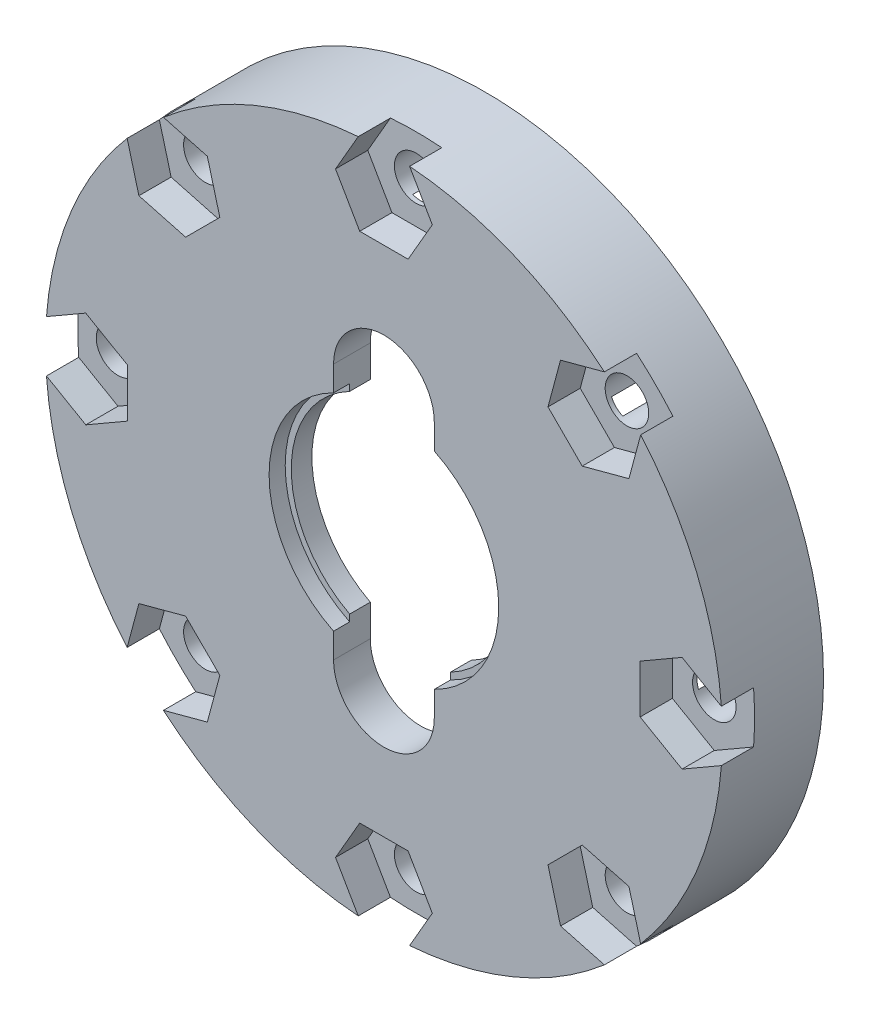
SolidWorks part; units mm, degrees
ref_plane "Front Plane" through (0, 0, 0) normal (0, 0, 1) x (1, 0, 0)
ref_plane "Top Plane" through (0, 0, 0) normal (0, 1, 0) x (1, 0, 0)
ref_plane "Right Plane" through (0, 0, 0) normal (1, 0, 0) x (0, 0, -1)
ref_axis "Z" through (0, 0, -6.594) along (0, 0, 1)
sketch "Sketch3" plane through (0, 0, 0) normal (0, 0, 1) x (1, 0, 0)
  line L0 (-3.125, -6.4031) -> (-3.125, -7.9497)
  line L1 (-3.125, -7.9497) -> (3.125, -7.9497)
  line L2 (3.125, -7.9497) -> (3.125, -6.4031)
  line L3 (3.125, 6.4031) -> (3.125, 7.9494)
  line L4 (3.125, 7.9494) -> (-3.125, 7.9494)
  line L5 (-3.125, 7.9494) -> (-3.125, 6.4031)
  line L132 (3.05, 6.3548) -> (3.05, 6.3561) construction
  line L133 (-3.05, 6.3561) -> (-3.05, 6.3548) construction
  line L134 (3.05, -6.3561) -> (3.05, -6.355) construction
  line L135 (-3.05, -6.355) -> (-3.05, -6.3561) construction
  line L198 (3.05, 6.3548) -> (3.05, 7.8744)
  line L199 (3.05, 7.8744) -> (-3.05, 7.8744)
  line L200 (-3.05, 7.8744) -> (-3.05, 6.3548)
  line L201 (-3.05, 6.3548) -> (-3.4914, 6.1247)
  line L202 (-3.4914, 6.1247) -> (-3.9416, 5.8451)
  line L203 (-3.9416, 5.8451) -> (-4.3696, 5.5325)
  line L204 (-4.3696, 5.5325) -> (-4.7729, 5.1886)
  line L205 (-4.7729, 5.1886) -> (-5.1492, 4.8154)
  line L206 (-5.1492, 4.8154) -> (-5.4964, 4.4149)
  line L207 (-5.4964, 4.4149) -> (-5.8125, 3.9896)
  line L208 (-5.8125, 3.9896) -> (-6.0958, 3.5417)
  line L209 (-6.0958, 3.5417) -> (-6.3446, 3.0737)
  line L210 (-6.3446, 3.0737) -> (-6.5576, 2.5884)
  line L211 (-6.5576, 2.5884) -> (-6.7335, 2.0885)
  line L212 (-6.7335, 2.0885) -> (-6.8714, 1.5768)
  line L213 (-6.8714, 1.5768) -> (-6.9705, 1.0561)
  line L214 (-6.9705, 1.0561) -> (-7.0301, 0.5295)
  line L215 (-7.0301, 0.5295) -> (-7.05, -0.0001)
  line L216 (-7.05, -0.0001) -> (-7.0301, -0.5297)
  line L217 (-7.0301, -0.5297) -> (-6.9705, -1.0563)
  line L218 (-6.9705, -1.0563) -> (-6.8714, -1.577)
  line L219 (-6.8714, -1.577) -> (-6.7335, -2.0887)
  line L220 (-6.7335, -2.0887) -> (-6.5576, -2.5887)
  line L221 (-6.5576, -2.5887) -> (-6.3446, -3.074)
  line L222 (-6.3446, -3.074) -> (-6.0958, -3.5419)
  line L223 (-6.0958, -3.5419) -> (-5.8125, -3.9898)
  line L224 (-5.8125, -3.9898) -> (-5.4964, -4.4152)
  line L225 (-5.4964, -4.4152) -> (-5.1492, -4.8156)
  line L226 (-5.1492, -4.8156) -> (-4.7729, -5.1888)
  line L227 (-4.7729, -5.1888) -> (-4.3696, -5.5327)
  line L228 (-4.3696, -5.5327) -> (-3.9416, -5.8453)
  line L229 (-3.9416, -5.8453) -> (-3.4914, -6.1249)
  line L230 (-3.4914, -6.1249) -> (-3.05, -6.355)
  line L231 (-3.05, -6.355) -> (-3.05, -7.8747)
  line L232 (-3.05, -7.8747) -> (3.05, -7.8747)
  line L233 (3.05, -7.8747) -> (3.05, -6.355)
  line L234 (3.05, -6.355) -> (3.4914, -6.1249)
  line L235 (3.4914, -6.1249) -> (3.9417, -5.8453)
  line L236 (3.9417, -5.8453) -> (4.3696, -5.5327)
  line L237 (4.3696, -5.5327) -> (4.7729, -5.1888)
  line L238 (4.7729, -5.1888) -> (5.1492, -4.8156)
  line L239 (5.1492, -4.8156) -> (5.4964, -4.4152)
  line L240 (5.4964, -4.4152) -> (5.8125, -3.9898)
  line L241 (5.8125, -3.9898) -> (6.0958, -3.5419)
  line L242 (6.0958, -3.5419) -> (6.3447, -3.074)
  line L243 (6.3447, -3.074) -> (6.5576, -2.5887)
  line L244 (6.5576, -2.5887) -> (6.7336, -2.0887)
  line L245 (6.7336, -2.0887) -> (6.8714, -1.577)
  line L246 (6.8714, -1.577) -> (6.9705, -1.0563)
  line L247 (6.9705, -1.0563) -> (7.0301, -0.5297)
  line L248 (7.0301, -0.5297) -> (7.05, -0.0001)
  line L249 (7.05, -0.0001) -> (7.0301, 0.5295)
  line L250 (7.0301, 0.5295) -> (6.9705, 1.0561)
  line L251 (6.9705, 1.0561) -> (6.8714, 1.5768)
  line L252 (6.8714, 1.5768) -> (6.7336, 2.0885)
  line L253 (6.7336, 2.0885) -> (6.5576, 2.5884)
  line L254 (6.5576, 2.5884) -> (6.3447, 3.0737)
  line L255 (6.3447, 3.0737) -> (6.0958, 3.5417)
  line L256 (6.0958, 3.5417) -> (5.8125, 3.9896)
  line L257 (5.8125, 3.9896) -> (5.4964, 4.4149)
  line L258 (5.4964, 4.4149) -> (5.1492, 4.8154)
  line L259 (5.1492, 4.8154) -> (4.7729, 5.1886)
  line L260 (4.7729, 5.1886) -> (4.3696, 5.5325)
  line L261 (4.3696, 5.5325) -> (3.9417, 5.8451)
  line L262 (3.9417, 5.8451) -> (3.4914, 6.1247)
  line L263 (3.4914, 6.1247) -> (3.05, 6.3548)
  line L264 (3.05, 6.3561) -> (3.05, 7.8744) construction
  line L265 (3.05, 7.8744) -> (-3.05, 7.8744) construction
  line L266 (-3.05, 7.8744) -> (-3.05, 6.3561) construction
  line L297 (-3.05, -6.3561) -> (-3.05, -7.8747) construction
  line L298 (-3.05, -7.8747) -> (3.05, -7.8747) construction
  line L299 (3.05, -7.8747) -> (3.05, -6.3561) construction
  arc A1 (-3.05, 6.3561) -> (-3.05, -6.3561) centre (0, 0) ccw construction
  arc A2 (3.05, 6.3561) -> (-3.05, 6.3561) centre (0, 0) ccw construction
  arc A3 (3.05, -6.3561) -> (3.05, 6.3561) centre (0, 0) ccw construction
  arc A4 (-3.05, -6.3561) -> (3.05, -6.3561) centre (0, 0) ccw construction
  circle A5 centre (0, 0) radius 21
  arc A6 (-3.125, 6.4031) -> (-3.125, -6.4031) centre (0, 0) ccw
  arc A7 (3.125, -6.4031) -> (3.125, 6.4031) centre (0, 0) ccw
  dimension "D1" = 14.1
  dimension "D3" = 42
  dimension "D2" = 0.075
  dimension "D4" = 0.075
extrude "Boss-Extrude2" add sketch "Sketch3" against normal blind 1
sketch "Sketch4" plane through (0, 0, -1) normal (0, 0, -1) x (-1, 0, 0)
  line L39 (2.75, 6.1644) -> (2.75, 7.5744)
  line L40 (2.75, 7.5744) -> (-2.75, 7.5744)
  line L41 (-2.75, 7.5744) -> (-2.75, 6.1644)
  line L42 (-2.75, -6.1644) -> (-2.75, -7.5747)
  line L43 (-2.75, -7.5747) -> (2.75, -7.5747)
  line L44 (2.75, -7.5747) -> (2.75, -6.1644)
  circle A14 centre (0, 0) radius 21
  arc A17 (-2.75, 6.1644) -> (-2.75, -6.1644) centre (0, 0) ccw
  arc A18 (2.75, -6.1644) -> (2.75, 6.1644) centre (0, 0) ccw
  dimension "D1" = 42
extrude "Boss-Extrude3" add sketch "Sketch4" along normal blind 5.28
sketch "Sketch5" plane through (0, 0, -6.28) normal (0, 0, -1) x (-1, 0, 0)
  circle A0 centre (0, 0) radius 17.25
  dimension "D1" = 34.5
extrude "Cut-Extrude1" cut sketch "Sketch5" against normal blind 4
sketch "Sketch6" plane through (0, 0, 0) normal (0, 0, 1) x (1, 0, 0)
  line L0 (0, 0) -> (-18.5, 0) construction
  line L1 (-16.3801, 0) -> (0, 0) construction
  line L3 (-21.1, -1.5011) -> (-18.5, -3.0022)
  line L4 (-18.5, -3.0022) -> (-15.9, -1.5011)
  line L5 (-15.9, -1.5011) -> (-15.9, 1.5011)
  line L6 (-15.9, 1.5011) -> (-18.5, 3.0022)
  line L7 (-18.5, 3.0022) -> (-21.1, 1.5011)
  line L8 (-21.1, 1.5011) -> (-21.1, -1.5011)
  circle A0 centre (-18.5, 0) radius 2.6 construction
  dimension "D1" = 0
  dimension "D2" = 18.5
  dimension "D3" = 5.2
extrude "Cut-Extrude2" cut sketch "Sketch6" against normal blind 2
sketch "Sketch8" plane through (0, 0, 0) normal (0, 0, 1) x (1, 0, 0)
  line L0 (36.6653, 0) -> (49.0214, 0) construction
  line L1 (0, 0) -> (-18.5, 0) construction
  circle A0 centre (0, 0) radius 18.5 construction
  circle A1 centre (-18.5, 0) radius 1.35
  dimension "D1" = 37
  dimension "D3" = 2.7
  dimension "D2" = 0
extrude "Cut-Extrude4" cut sketch "Sketch8" against normal through all
pattern_circular "CirPattern1" count 8 over 360 about axis through (0, 0, -6.594) along (0, 0, 1) of "Cut-Extrude2", "Cut-Extrude4"
ref_plane "Plane4" through (0, 0, 0) normal (-0.7071, 0.7071, 0) x (0, 0, 1)
sketch "Sketch9" plane through (0, 0, 0) normal (0, 0, 1) x (1, 0, 0)
  line L1 (-3.125, 7.9494) -> (-3.125, 10.495) construction
  line L2 (0, 0) -> (3.8744, 0) construction
  line L4 (3.125, 7.9494) -> (3.125, -7.9494)
  line L5 (-3.125, 7.9494) -> (-3.125, -7.9494)
  arc A0 (-3.125, 7.9494) -> (3.125, 7.9494) centre (0, 7.9494) cw
  arc A1 (-3.125, -7.9494) -> (3.125, -7.9494) centre (0, -7.9494) ccw
extrude "Cut-Extrude5" cut sketch "Sketch9" against normal through all
equation "\"BearingOD\"= 32"
equation "\"BearingID\"= 25"
equation "\"BearingHeight\"= 4"
equation "\"RetainingRingThickness\"= 1.30"
equation "\"BearingBaseDistance\"= 17.2 - 2*\"BearingHeight\"  - \"RetainingRingThickness\"*2"
equation "\"SeatsOD\"= \"BearingOD\" + 10"
equation "\"WireHarnessHeight\"= 4"
equation "\"OuterWallWidth\"= 6"
equation "\"OverallOD\"= 42"
equation "\"OuterHousingHeight\"= \"WireHarnessHeight\" + \"BearingHeight\"*2 + \"BearingBaseDistance\""
equation "\"RetaininRingGrooveDiameter\"= 23.9"
equation "\"ShaftLengthAfterFlange\"= 2*\"BearingHeight\" + \"BearingBaseDistance\" + \"RetainingRingThickness\"*2\t'give a retaining ring thickness of extra clearance"
equation "\"RetainingRingGrooveBase\"= \"ShaftLengthAfterFlange\" - \"RetainingRingThickness\"*2"
equation "\"CoverThickness\"= 1"
equation "\"CoverClearance\"= 1"
equation "\"FlangHeight\"= 3"
equation "\"PCBWidth\"= 5"
equation "\"PCBHeight\"= \"OuterHousingHeight\" "
equation "\"PCBThickness\"= 1"
equation "\"NormalDistSidewallPCBToZ\"= (\"OverallOD\"/2) - 1.6\t'radial distance from the z axis to pcb origin on the top/connector side"
equation "\"PCBSidewallCutoutClearance\"= 0.1"
equation "\"OutputHubBoltCircleRadius\"= 8"
equation "\"OutputHubOD\"= 27"
equation "\"StatorWireRadius\"= \"NormalDistSidewallPCBToZ\" - 5.7"
equation "\"MountingHoleRadius\"= (\"OverallOD\"+\"BearingOD\")/4"
equation "\"D3@Sketch3\"=\"OverallOD\""
equation "\"D1@Sketch4\"=\"OverallOD\""
equation "\"D1@Sketch8\"=\"MountingHoleRadius\"*2"
equation "\"D2@Sketch6\"=(\"OverallOD\"+\"BearingOD\")/4"
